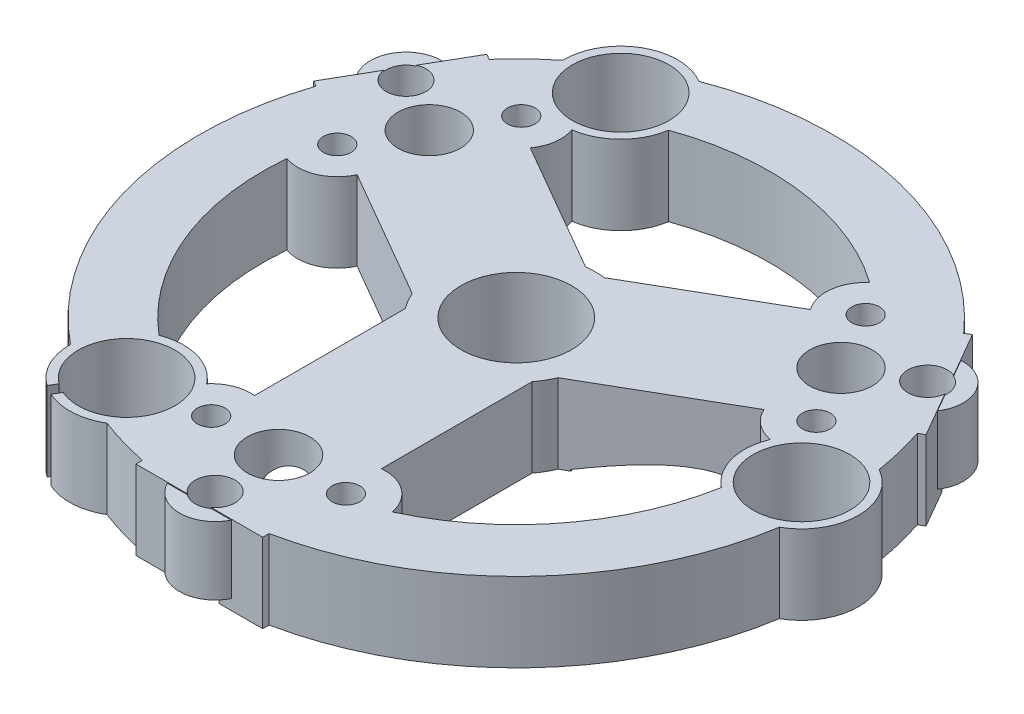
SolidWorks part; units mm, degrees
note: '?' marks a value the reader was unsure of.
other "Moving Tensegrity Frame"
ref_plane "Front Plane" through (0, 0, 0) normal (0, 0, 1) x (1, 0, 0)
ref_plane "Top Plane" through (0, 0, 0) normal (0, 1, 0) x (1, 0, 0)
ref_plane "Right Plane" through (0, 0, 0) normal (1, 0, 0) x (0, 0, -1)
sketch3d "Main Profile Sketch datum points"
  point P0 (0, 96, 0)
  point P1 (10, 96, 0)
  point P2 (0, 96, 10)
ref_plane "Main Profile Sketch plane" through (0, 96, 0) normal (0, -1, 0) x (-1, 0, 0)
sketch "Main Profile Sketch" plane through (0, 96, 0) normal (0, -1, 0) x (-1, 0, 0)
  line L0 (77.2684, -37.7328) -> (76.7153, -36.7748)
  line L1 (77.9277, -36.0748) -> (78.4808, -37.0328)
  line L2 (94.9327, 13.0718) -> (94.2328, 12.6677)
  line L3 (92.1817, 17.8367) -> (94.9327, 13.0718)
  line L4 (86.9327, 26.9282) -> (89.6837, 22.1633)
  line L5 (86.2328, 26.5241) -> (86.9327, 26.9282)
  line L6 (25.6506, 26.9282) -> (26.3505, 26.5241)
  line L7 (22.8996, 22.1633) -> (25.6506, 26.9282)
  line L8 (17.6506, 13.0718) -> (20.4016, 17.8367)
  line L9 (18.3505, 12.6677) -> (17.6506, 13.0718)
  line L10 (48.2917, -40) -> (48.2917, -39.1918)
  line L11 (53.7937, -40) -> (48.2917, -40)
  line L12 (64.2917, -40) -> (58.7897, -40)
  line L13 (64.2917, -39.1918) -> (64.2917, -40)
  line L14 (57.4878, 9.9282) -> (73.964, 19.4407)
  line L15 (38.6193, 19.4407) -> (55.0955, 9.9282)
  line L16 (64.2917, -6) -> (64.2917, -25.0251)
  line L17 (81.964, 5.5843) -> (65.4878, -3.9282)
  line L18 (47.0955, -3.9282) -> (30.6193, 5.5843)
  line L19 (48.2917, -25.0251) -> (48.2917, -6)
  arc A0 (77.9277, -36.0748) -> (76.7153, -36.7748) centre (74.2917, -31.1769) ccw
  arc A1 (78.4808, -37.0328) -> (81.4908, -31.0645) centre (74.2917, -31.1769) ccw
  arc A2 (81.4908, -31.0645) -> (94.2328, 12.6677) centre (56.2917, 0) ccw
  arc A3 (89.6837, 22.1633) -> (92.1817, 17.8367) centre (89.2006, 19) ccw
  arc A4 (86.2328, 26.5241) -> (81.4908, 31.0645) centre (56.2917, 0) ccw
  arc A5 (81.4908, 31.0645) -> (70.5948, 37.3553) centre (74.2917, 31.1769) ccw
  arc A6 (70.5948, 37.3553) -> (26.3505, 26.5241) centre (56.2917, 0) ccw
  arc A7 (20.4016, 17.8367) -> (22.8996, 22.1633) centre (23.3827, 19) ccw
  arc A8 (18.3505, 12.6677) -> (16.7894, 6.2908) centre (56.2917, 0) ccw
  arc A9 (16.7894, 6.2908) -> (16.7894, -6.2908) centre (20.2917, 0) ccw
  arc A10 (16.7894, -6.2908) -> (48.2917, -39.1918) centre (56.2917, 0) ccw
  arc A11 (58.7897, -40) -> (53.7937, -40) centre (56.2917, -38) ccw
  arc A12 (64.2917, -39.1918) -> (70.5948, -37.3553) centre (56.2917, 0) ccw
  arc A13 (70.5948, -37.3553) -> (77.2684, -37.7328) centre (74.2917, -31.1769) ccw
  circle A14 centre (74.2917, 31.1769) radius 6.1
  arc A15 (38.6193, 19.4407) -> (37.8344, 26.1406) centre (34.5609, 22.3612) ccw
  arc A16 (67.1737, 30.0929) -> (37.8344, 26.1406) centre (56.2917, 0) ccw
  arc A17 (67.1737, 30.0929) -> (73.314, 24.0436) centre (74.2917, 31.1769) ccw
  arc A18 (73.314, 24.0436) -> (73.964, 19.4407) centre (78.0224, 22.3612) ccw
  arc A19 (57.4878, 9.9282) -> (55.0955, 9.9282) centre (56.2917, 0) ccw
  arc A20 (68.6029, -26.7636) -> (64.2917, -25.0251) centre (64.7917, -30) ccw
  arc A21 (64.2917, -6) -> (65.4878, -3.9282) centre (56.2917, 0) ccw
  arc A22 (81.964, 5.5843) -> (88.1587, 2.9141) centre (86.5224, 7.6388) ccw
  arc A23 (76.9118, -24.4706) -> (88.1587, 2.9141) centre (56.2917, 0) ccw
  arc A24 (76.9118, -24.4706) -> (68.6029, -26.7636) centre (74.2917, -31.1769) ccw
  circle A25 centre (20.2917, 0) radius 6.1
  arc A26 (48.2917, -25.0251) -> (42.8818, -29.0547) centre (47.7917, -30) ccw
  arc A27 (24.7894, -5.6223) -> (42.8818, -29.0547) centre (56.2917, 0) ccw
  arc A28 (24.7894, -5.6223) -> (26.9581, 2.7199) centre (20.2917, 0) ccw
  arc A29 (26.9581, 2.7199) -> (30.6193, 5.5843) centre (26.0609, 7.6388) ccw
  arc A30 (47.0955, -3.9282) -> (48.2917, -6) centre (56.2917, 0) ccw
extrude "Main Extrusion" add sketch "Main Profile Sketch" against normal blind 1 separate body
sketch3d "Detail Profile 2 Sketch datum points"
  point P0 (0, 97, 0)
  point P1 (10, 97, 0)
  point P2 (0, 97, 10)
ref_plane "Detail Profile 2 Sketch plane" through (0, 97, 0) normal (0, -1, 0) x (-1, 0, 0)
sketch "Detail Profile 2 Sketch" plane through (0, 97, 0) normal (0, -1, 0) x (-1, 0, 0)
  line L0 (77.2684, -37.7328) -> (76.7153, -36.7748)
  line L1 (77.9277, -36.0748) -> (78.4808, -37.0328)
  line L2 (94.9327, 13.0718) -> (94.2328, 12.6677)
  line L3 (92.1817, 17.8367) -> (94.9327, 13.0718)
  line L4 (86.9327, 26.9282) -> (89.6837, 22.1633)
  line L5 (86.2328, 26.5241) -> (86.9327, 26.9282)
  line L6 (25.6506, 26.9282) -> (26.3505, 26.5241)
  line L7 (22.8996, 22.1633) -> (25.6506, 26.9282)
  line L8 (17.6506, 13.0718) -> (20.4016, 17.8367)
  line L9 (18.3505, 12.6677) -> (17.6506, 13.0718)
  line L10 (48.2917, -40) -> (48.2917, -39.1918)
  line L11 (53.7937, -40) -> (48.2917, -40)
  line L12 (64.2917, -40) -> (58.7897, -40)
  line L13 (64.2917, -39.1918) -> (64.2917, -40)
  line L14 (79.1224, 17.3833) -> (79.1224, 12.6167)
  line L15 (57.4878, 9.9282) -> (73.964, 19.4407)
  line L16 (38.6193, 19.4407) -> (55.0955, 9.9282)
  line L17 (64.2917, -6) -> (64.2917, -25.0251)
  line L18 (81.964, 5.5843) -> (65.4878, -3.9282)
  line L19 (59.9306, -28.4637) -> (55.8027, -26.0804)
  line L20 (29.8219, 11.0804) -> (33.9499, 13.4637)
  line L21 (47.0955, -3.9282) -> (30.6193, 5.5843)
  line L22 (48.2917, -25.0251) -> (48.2917, -6)
  arc A0 (77.9277, -36.0748) -> (76.7153, -36.7748) centre (74.2917, -31.1769) ccw
  arc A1 (78.4808, -37.0328) -> (81.4908, -31.0645) centre (74.2917, -31.1769) ccw
  arc A2 (81.4908, -31.0645) -> (94.2328, 12.6677) centre (56.2917, 0) ccw
  arc A3 (89.6837, 22.1633) -> (92.1817, 17.8367) centre (89.2006, 19) ccw
  arc A4 (86.2328, 26.5241) -> (81.4908, 31.0645) centre (56.2917, 0) ccw
  arc A5 (81.4908, 31.0645) -> (70.5948, 37.3553) centre (74.2917, 31.1769) ccw
  arc A6 (70.5948, 37.3553) -> (26.3505, 26.5241) centre (56.2917, 0) ccw
  arc A7 (20.4016, 17.8367) -> (22.8996, 22.1633) centre (23.3827, 19) ccw
  arc A8 (18.3505, 12.6677) -> (16.7894, 6.2908) centre (56.2917, 0) ccw
  arc A9 (16.7894, 6.2908) -> (16.7894, -6.2908) centre (20.2917, 0) ccw
  arc A10 (16.7894, -6.2908) -> (48.2917, -39.1918) centre (56.2917, 0) ccw
  arc A11 (58.7897, -40) -> (53.7937, -40) centre (56.2917, -38) ccw
  arc A12 (64.2917, -39.1918) -> (70.5948, -37.3553) centre (56.2917, 0) ccw
  arc A13 (70.5948, -37.3553) -> (77.2684, -37.7328) centre (74.2917, -31.1769) ccw
  arc A14 (79.1224, 12.6167) -> (79.1224, 17.3833) centre (82.2724, 15) ccw
  circle A15 centre (74.2917, 31.1769) radius 6.1
  arc A16 (38.6193, 19.4407) -> (37.8344, 26.1406) centre (34.5609, 22.3612) ccw
  arc A17 (67.1737, 30.0929) -> (37.8344, 26.1406) centre (56.2917, 0) ccw
  arc A18 (67.1737, 30.0929) -> (73.314, 24.0436) centre (74.2917, 31.1769) ccw
  arc A19 (73.314, 24.0436) -> (73.964, 19.4407) centre (78.0224, 22.3612) ccw
  arc A20 (57.4878, 9.9282) -> (55.0955, 9.9282) centre (56.2917, 0) ccw
  arc A21 (68.6029, -26.7636) -> (64.2917, -25.0251) centre (64.7917, -30) ccw
  arc A22 (64.2917, -6) -> (65.4878, -3.9282) centre (56.2917, 0) ccw
  arc A23 (81.964, 5.5843) -> (88.1587, 2.9141) centre (86.5224, 7.6388) ccw
  arc A24 (76.9118, -24.4706) -> (88.1587, 2.9141) centre (56.2917, 0) ccw
  arc A25 (76.9118, -24.4706) -> (68.6029, -26.7636) centre (74.2917, -31.1769) ccw
  arc A26 (55.8027, -26.0804) -> (52.3417, -30) centre (56.2917, -30) ccw
  arc A27 (52.3417, -30) -> (59.9306, -28.4637) centre (56.2917, -30) ccw
  arc A28 (33.9499, 13.4637) -> (26.3609, 15) centre (30.3109, 15) ccw
  arc A29 (26.3609, 15) -> (29.8219, 11.0804) centre (30.3109, 15) ccw
  circle A30 centre (20.2917, 0) radius 6.1
  arc A31 (48.2917, -25.0251) -> (42.8818, -29.0547) centre (47.7917, -30) ccw
  arc A32 (24.7894, -5.6223) -> (42.8818, -29.0547) centre (56.2917, 0) ccw
  arc A33 (24.7894, -5.6223) -> (26.9581, 2.7199) centre (20.2917, 0) ccw
  arc A34 (26.9581, 2.7199) -> (30.6193, 5.5843) centre (26.0609, 7.6388) ccw
  arc A35 (47.0955, -3.9282) -> (48.2917, -6) centre (56.2917, 0) ccw
extrude "Detail Extrusion 2" add sketch "Detail Profile 2 Sketch" against normal blind 0.31
sketch3d "Detail Profile 3 Sketch datum points"
  point P0 (0, 97.31, 0)
  point P1 (10, 97.31, 0)
  point P2 (0, 97.31, 10)
ref_plane "Detail Profile 3 Sketch plane" through (0, 97.31, 0) normal (0, -1, 0) x (-1, 0, 0)
sketch "Detail Profile 3 Sketch" plane through (0, 97.31, 0) normal (0, -1, 0) x (-1, 0, 0)
  line L0 (77.2684, -37.7328) -> (76.7153, -36.7748)
  line L1 (77.9277, -36.0748) -> (78.4808, -37.0328)
  line L2 (94.9327, 13.0718) -> (94.2328, 12.6677)
  line L3 (92.9482, 16.5089) -> (94.9327, 13.0718)
  line L4 (86.9327, 26.9282) -> (88.9171, 23.4911)
  line L5 (86.2328, 26.5241) -> (86.9327, 26.9282)
  line L6 (25.6506, 26.9282) -> (26.3505, 26.5241)
  line L7 (23.6662, 23.4911) -> (25.6506, 26.9282)
  line L8 (17.6506, 13.0718) -> (19.6351, 16.5089)
  line L9 (18.3505, 12.6677) -> (17.6506, 13.0718)
  line L10 (48.2917, -40) -> (48.2917, -39.1918)
  line L11 (52.2605, -40) -> (48.2917, -40)
  line L12 (64.2917, -40) -> (60.3228, -40)
  line L13 (64.2917, -39.1918) -> (64.2917, -40)
  line L14 (79.1224, 17.3833) -> (79.1224, 12.6167)
  line L15 (57.4878, 9.9282) -> (73.964, 19.4407)
  line L16 (38.6193, 19.4407) -> (55.0955, 9.9282)
  line L17 (64.2917, -6) -> (64.2917, -25.0251)
  line L18 (81.964, 5.5843) -> (65.4878, -3.9282)
  line L19 (59.9306, -28.4637) -> (55.8027, -26.0804)
  line L20 (29.8219, 11.0804) -> (33.9499, 13.4637)
  line L21 (47.0955, -3.9282) -> (30.6193, 5.5843)
  line L22 (48.2917, -25.0251) -> (48.2917, -6)
  arc A0 (77.9277, -36.0748) -> (76.7153, -36.7748) centre (74.2917, -31.1769) ccw
  arc A1 (78.4808, -37.0328) -> (81.4908, -31.0645) centre (74.2917, -31.1769) ccw
  arc A2 (81.4908, -31.0645) -> (94.2328, 12.6677) centre (56.2917, 0) ccw
  arc A3 (92.9482, 16.5089) -> (88.9171, 23.4911) centre (89.2006, 19) ccw
  arc A4 (86.2328, 26.5241) -> (81.4908, 31.0645) centre (56.2917, 0) ccw
  arc A5 (81.4908, 31.0645) -> (70.5948, 37.3553) centre (74.2917, 31.1769) ccw
  arc A6 (70.5948, 37.3553) -> (26.3505, 26.5241) centre (56.2917, 0) ccw
  arc A7 (23.6662, 23.4911) -> (19.6351, 16.5089) centre (23.3827, 19) ccw
  arc A8 (18.3505, 12.6677) -> (16.7894, 6.2908) centre (56.2917, 0) ccw
  arc A9 (16.7894, 6.2908) -> (16.7894, -6.2908) centre (20.2917, 0) ccw
  arc A10 (16.7894, -6.2908) -> (48.2917, -39.1918) centre (56.2917, 0) ccw
  arc A11 (52.2605, -40) -> (60.3228, -40) centre (56.2917, -38) ccw
  arc A12 (64.2917, -39.1918) -> (70.5948, -37.3553) centre (56.2917, 0) ccw
  arc A13 (70.5948, -37.3553) -> (77.2684, -37.7328) centre (74.2917, -31.1769) ccw
  circle A14 centre (89.2006, 19) radius 2.5
  arc A15 (79.1224, 12.6167) -> (79.1224, 17.3833) centre (82.2724, 15) ccw
  circle A16 centre (74.2917, 31.1769) radius 6.1
  arc A17 (38.6193, 19.4407) -> (37.8344, 26.1406) centre (34.5609, 22.3612) ccw
  arc A18 (67.1737, 30.0929) -> (37.8344, 26.1406) centre (56.2917, 0) ccw
  arc A19 (67.1737, 30.0929) -> (73.314, 24.0436) centre (74.2917, 31.1769) ccw
  arc A20 (73.314, 24.0436) -> (73.964, 19.4407) centre (78.0224, 22.3612) ccw
  arc A21 (57.4878, 9.9282) -> (55.0955, 9.9282) centre (56.2917, 0) ccw
  arc A22 (68.6029, -26.7636) -> (64.2917, -25.0251) centre (64.7917, -30) ccw
  arc A23 (64.2917, -6) -> (65.4878, -3.9282) centre (56.2917, 0) ccw
  arc A24 (81.964, 5.5843) -> (88.1587, 2.9141) centre (86.5224, 7.6388) ccw
  arc A25 (76.9118, -24.4706) -> (88.1587, 2.9141) centre (56.2917, 0) ccw
  arc A26 (76.9118, -24.4706) -> (68.6029, -26.7636) centre (74.2917, -31.1769) ccw
  arc A27 (55.8027, -26.0804) -> (52.3417, -30) centre (56.2917, -30) ccw
  arc A28 (52.3417, -30) -> (59.9306, -28.4637) centre (56.2917, -30) ccw
  circle A29 centre (56.2917, -38) radius 2.5
  arc A30 (33.9499, 13.4637) -> (26.3609, 15) centre (30.3109, 15) ccw
  arc A31 (26.3609, 15) -> (29.8219, 11.0804) centre (30.3109, 15) ccw
  circle A32 centre (23.3827, 19) radius 2.5
  circle A33 centre (20.2917, 0) radius 6.1
  arc A34 (48.2917, -25.0251) -> (42.8818, -29.0547) centre (47.7917, -30) ccw
  arc A35 (24.7894, -5.6223) -> (42.8818, -29.0547) centre (56.2917, 0) ccw
  arc A36 (24.7894, -5.6223) -> (26.9581, 2.7199) centre (20.2917, 0) ccw
  arc A37 (26.9581, 2.7199) -> (30.6193, 5.5843) centre (26.0609, 7.6388) ccw
  arc A38 (47.0955, -3.9282) -> (48.2917, -6) centre (56.2917, 0) ccw
extrude "Detail Extrusion 3" add sketch "Detail Profile 3 Sketch" against normal blind 0.4
sketch3d "Detail Profile 4 Sketch datum points"
  point P0 (0, 97.71, 0)
  point P1 (10, 97.71, 0)
  point P2 (0, 97.71, 10)
ref_plane "Detail Profile 4 Sketch plane" through (0, 97.71, 0) normal (0, -1, 0) x (-1, 0, 0)
sketch "Detail Profile 4 Sketch" plane through (0, 97.71, 0) normal (0, -1, 0) x (-1, 0, 0)
  line L0 (77.2684, -37.7328) -> (76.7153, -36.7748)
  line L1 (77.9277, -36.0748) -> (78.4808, -37.0328)
  line L2 (94.9327, 13.0718) -> (94.2328, 12.6677)
  line L3 (92.9482, 16.5089) -> (94.9327, 13.0718)
  line L4 (86.9327, 26.9282) -> (88.9171, 23.4911)
  line L5 (86.2328, 26.5241) -> (86.9327, 26.9282)
  line L6 (25.6506, 26.9282) -> (26.3505, 26.5241)
  line L7 (23.6662, 23.4911) -> (25.6506, 26.9282)
  line L8 (17.6506, 13.0718) -> (19.6351, 16.5089)
  line L9 (18.3505, 12.6677) -> (17.6506, 13.0718)
  line L10 (48.2917, -40) -> (48.2917, -39.1918)
  line L11 (52.2605, -40) -> (48.2917, -40)
  line L12 (64.2917, -40) -> (60.3228, -40)
  line L13 (64.2917, -39.1918) -> (64.2917, -40)
  line L14 (57.4878, 9.9282) -> (73.964, 19.4407)
  line L15 (38.6193, 19.4407) -> (55.0955, 9.9282)
  line L16 (64.2917, -6) -> (64.2917, -25.0251)
  line L17 (81.964, 5.5843) -> (65.4878, -3.9282)
  line L18 (47.0955, -3.9282) -> (30.6193, 5.5843)
  line L19 (48.2917, -25.0251) -> (48.2917, -6)
  arc A0 (77.9277, -36.0748) -> (76.7153, -36.7748) centre (74.2917, -31.1769) ccw
  arc A1 (78.4808, -37.0328) -> (81.4908, -31.0645) centre (74.2917, -31.1769) ccw
  arc A2 (81.4908, -31.0645) -> (94.2328, 12.6677) centre (56.2917, 0) ccw
  arc A3 (92.9482, 16.5089) -> (88.9171, 23.4911) centre (89.2006, 19) ccw
  arc A4 (86.2328, 26.5241) -> (81.4908, 31.0645) centre (56.2917, 0) ccw
  arc A5 (81.4908, 31.0645) -> (70.5948, 37.3553) centre (74.2917, 31.1769) ccw
  arc A6 (70.5948, 37.3553) -> (26.3505, 26.5241) centre (56.2917, 0) ccw
  arc A7 (23.6662, 23.4911) -> (19.6351, 16.5089) centre (23.3827, 19) ccw
  arc A8 (18.3505, 12.6677) -> (16.7894, 6.2908) centre (56.2917, 0) ccw
  arc A9 (16.7894, 6.2908) -> (16.7894, -6.2908) centre (20.2917, 0) ccw
  arc A10 (16.7894, -6.2908) -> (48.2917, -39.1918) centre (56.2917, 0) ccw
  arc A11 (52.2605, -40) -> (60.3228, -40) centre (56.2917, -38) ccw
  arc A12 (64.2917, -39.1918) -> (70.5948, -37.3553) centre (56.2917, 0) ccw
  arc A13 (70.5948, -37.3553) -> (77.2684, -37.7328) centre (74.2917, -31.1769) ccw
  circle A14 centre (89.2006, 19) radius 2.5
  circle A15 centre (82.2724, 15) radius 3.95
  circle A16 centre (74.2917, 31.1769) radius 6.1
  arc A17 (38.6193, 19.4407) -> (37.8344, 26.1406) centre (34.5609, 22.3612) ccw
  arc A18 (67.1737, 30.0929) -> (37.8344, 26.1406) centre (56.2917, 0) ccw
  arc A19 (67.1737, 30.0929) -> (73.314, 24.0436) centre (74.2917, 31.1769) ccw
  arc A20 (73.314, 24.0436) -> (73.964, 19.4407) centre (78.0224, 22.3612) ccw
  arc A21 (57.4878, 9.9282) -> (55.0955, 9.9282) centre (56.2917, 0) ccw
  arc A22 (68.6029, -26.7636) -> (64.2917, -25.0251) centre (64.7917, -30) ccw
  arc A23 (64.2917, -6) -> (65.4878, -3.9282) centre (56.2917, 0) ccw
  arc A24 (81.964, 5.5843) -> (88.1587, 2.9141) centre (86.5224, 7.6388) ccw
  arc A25 (76.9118, -24.4706) -> (88.1587, 2.9141) centre (56.2917, 0) ccw
  arc A26 (76.9118, -24.4706) -> (68.6029, -26.7636) centre (74.2917, -31.1769) ccw
  circle A27 centre (56.2917, -30) radius 3.95
  circle A28 centre (56.2917, -38) radius 2.5
  circle A29 centre (30.3109, 15) radius 3.95
  circle A30 centre (23.3827, 19) radius 2.5
  circle A31 centre (20.2917, 0) radius 6.1
  arc A32 (48.2917, -25.0251) -> (42.8818, -29.0547) centre (47.7917, -30) ccw
  arc A33 (24.7894, -5.6223) -> (42.8818, -29.0547) centre (56.2917, 0) ccw
  arc A34 (24.7894, -5.6223) -> (26.9581, 2.7199) centre (20.2917, 0) ccw
  arc A35 (26.9581, 2.7199) -> (30.6193, 5.5843) centre (26.0609, 7.6388) ccw
  arc A36 (47.0955, -3.9282) -> (48.2917, -6) centre (56.2917, 0) ccw
extrude "Detail Extrusion 4" add sketch "Detail Profile 4 Sketch" against normal blind 2.99
sketch3d "Detail Profile 5 Sketch datum points"
  point P0 (0, 100.7, 0)
  point P1 (10, 100.7, 0)
  point P2 (0, 100.7, 10)
ref_plane "Detail Profile 5 Sketch plane" through (0, 100.7, 0) normal (0, -1, 0) x (-1, 0, 0)
sketch "Detail Profile 5 Sketch" plane through (0, 100.7, 0) normal (0, -1, 0) x (-1, 0, 0)
  line L0 (77.2684, -37.7328) -> (76.7153, -36.7748)
  line L1 (77.9277, -36.0748) -> (78.4808, -37.0328)
  line L2 (94.9327, 13.0718) -> (94.2328, 12.6677)
  line L3 (92.9482, 16.5089) -> (94.9327, 13.0718)
  line L4 (86.9327, 26.9282) -> (88.9171, 23.4911)
  line L5 (86.2328, 26.5241) -> (86.9327, 26.9282)
  line L6 (25.6506, 26.9282) -> (26.3505, 26.5241)
  line L7 (23.6662, 23.4911) -> (25.6506, 26.9282)
  line L8 (17.6506, 13.0718) -> (19.6351, 16.5089)
  line L9 (18.3505, 12.6677) -> (17.6506, 13.0718)
  line L10 (48.2917, -40) -> (48.2917, -39.1918)
  line L11 (52.2605, -40) -> (48.2917, -40)
  line L12 (64.2917, -40) -> (60.3228, -40)
  line L13 (64.2917, -39.1918) -> (64.2917, -40)
  line L14 (57.4878, 9.9282) -> (73.964, 19.4407)
  line L15 (38.6193, 19.4407) -> (55.0955, 9.9282)
  line L16 (64.2917, -6) -> (64.2917, -25.0251)
  line L17 (81.964, 5.5843) -> (65.4878, -3.9282)
  line L18 (47.0955, -3.9282) -> (30.6193, 5.5843)
  line L19 (48.2917, -25.0251) -> (48.2917, -6)
  arc A0 (77.9277, -36.0748) -> (76.7153, -36.7748) centre (74.2917, -31.1769) ccw
  arc A1 (78.4808, -37.0328) -> (81.4908, -31.0645) centre (74.2917, -31.1769) ccw
  arc A2 (81.4908, -31.0645) -> (94.2328, 12.6677) centre (56.2917, 0) ccw
  arc A3 (92.9482, 16.5089) -> (88.9171, 23.4911) centre (89.2006, 19) ccw
  arc A4 (86.2328, 26.5241) -> (81.4908, 31.0645) centre (56.2917, 0) ccw
  arc A5 (81.4908, 31.0645) -> (70.5948, 37.3553) centre (74.2917, 31.1769) ccw
  arc A6 (70.5948, 37.3553) -> (26.3505, 26.5241) centre (56.2917, 0) ccw
  arc A7 (23.6662, 23.4911) -> (19.6351, 16.5089) centre (23.3827, 19) ccw
  arc A8 (18.3505, 12.6677) -> (16.7894, 6.2908) centre (56.2917, 0) ccw
  arc A9 (16.7894, 6.2908) -> (16.7894, -6.2908) centre (20.2917, 0) ccw
  arc A10 (16.7894, -6.2908) -> (48.2917, -39.1918) centre (56.2917, 0) ccw
  arc A11 (52.2605, -40) -> (60.3228, -40) centre (56.2917, -38) ccw
  arc A12 (64.2917, -39.1918) -> (70.5948, -37.3553) centre (56.2917, 0) ccw
  arc A13 (70.5948, -37.3553) -> (77.2684, -37.7328) centre (74.2917, -31.1769) ccw
  circle A14 centre (78.0224, 22.3612) radius 1.1
  circle A15 centre (89.2006, 19) radius 2.5
  circle A16 centre (86.5224, 7.6388) radius 1.1
  circle A17 centre (82.2724, 15) radius 3.95
  circle A18 centre (74.2917, 31.1769) radius 6.1
  arc A19 (38.6193, 19.4407) -> (37.8344, 26.1406) centre (34.5609, 22.3612) ccw
  arc A20 (67.1737, 30.0929) -> (37.8344, 26.1406) centre (56.2917, 0) ccw
  arc A21 (67.1737, 30.0929) -> (73.314, 24.0436) centre (74.2917, 31.1769) ccw
  arc A22 (73.314, 24.0436) -> (73.964, 19.4407) centre (78.0224, 22.3612) ccw
  arc A23 (57.4878, 9.9282) -> (55.0955, 9.9282) centre (56.2917, 0) ccw
  arc A24 (68.6029, -26.7636) -> (64.2917, -25.0251) centre (64.7917, -30) ccw
  arc A25 (64.2917, -6) -> (65.4878, -3.9282) centre (56.2917, 0) ccw
  arc A26 (81.964, 5.5843) -> (88.1587, 2.9141) centre (86.5224, 7.6388) ccw
  arc A27 (76.9118, -24.4706) -> (88.1587, 2.9141) centre (56.2917, 0) ccw
  arc A28 (76.9118, -24.4706) -> (68.6029, -26.7636) centre (74.2917, -31.1769) ccw
  circle A29 centre (64.7917, -30) radius 1.1
  circle A30 centre (56.2917, -30) radius 3.95
  circle A31 centre (56.2917, -38) radius 2.5
  circle A32 centre (34.5609, 22.3612) radius 1.1
  circle A33 centre (30.3109, 15) radius 3.95
  circle A34 centre (26.0609, 7.6388) radius 1.1
  circle A35 centre (23.3827, 19) radius 2.5
  circle A36 centre (20.2917, 0) radius 6.1
  arc A37 (48.2917, -25.0251) -> (42.8818, -29.0547) centre (47.7917, -30) ccw
  arc A38 (24.7894, -5.6223) -> (42.8818, -29.0547) centre (56.2917, 0) ccw
  arc A39 (24.7894, -5.6223) -> (26.9581, 2.7199) centre (20.2917, 0) ccw
  arc A40 (26.9581, 2.7199) -> (30.6193, 5.5843) centre (26.0609, 7.6388) ccw
  arc A41 (47.0955, -3.9282) -> (48.2917, -6) centre (56.2917, 0) ccw
  circle A42 centre (47.7917, -30) radius 1.1
extrude "Detail Extrusion 5" add sketch "Detail Profile 5 Sketch" against normal blind 1.3
sketch3d "Detail Profile 6 Sketch datum points"
  point P0 (0, 102, 0)
  point P1 (10, 102, 0)
  point P2 (0, 102, 10)
ref_plane "Detail Profile 6 Sketch plane" through (0, 102, 0) normal (0, -1, 0) x (-1, 0, 0)
sketch "Detail Profile 6 Sketch" plane through (0, 102, 0) normal (0, -1, 0) x (-1, 0, 0)
  line L0 (77.2684, -37.7328) -> (76.7153, -36.7748)
  line L1 (77.9277, -36.0748) -> (78.4808, -37.0328)
  line L2 (94.9327, 13.0718) -> (94.2328, 12.6677)
  line L3 (92.9482, 16.5089) -> (94.9327, 13.0718)
  line L4 (86.9327, 26.9282) -> (88.9171, 23.4911)
  line L5 (86.2328, 26.5241) -> (86.9327, 26.9282)
  line L6 (25.6506, 26.9282) -> (26.3505, 26.5241)
  line L7 (23.6662, 23.4911) -> (25.6506, 26.9282)
  line L8 (17.6506, 13.0718) -> (19.6351, 16.5089)
  line L9 (18.3505, 12.6677) -> (17.6506, 13.0718)
  line L10 (48.2917, -40) -> (48.2917, -39.1918)
  line L11 (52.2605, -40) -> (48.2917, -40)
  line L12 (64.2917, -40) -> (60.3228, -40)
  line L13 (64.2917, -39.1918) -> (64.2917, -40)
  line L14 (57.4878, 9.9282) -> (73.964, 19.4407)
  line L15 (38.6193, 19.4407) -> (55.0955, 9.9282)
  line L16 (64.2917, -6) -> (64.2917, -25.0251)
  line L17 (81.964, 5.5843) -> (65.4878, -3.9282)
  line L18 (47.0955, -3.9282) -> (30.6193, 5.5843)
  line L19 (48.2917, -25.0251) -> (48.2917, -6)
  arc A0 (77.9277, -36.0748) -> (76.7153, -36.7748) centre (74.2917, -31.1769) ccw
  arc A1 (78.4808, -37.0328) -> (81.4908, -31.0645) centre (74.2917, -31.1769) ccw
  arc A2 (81.4908, -31.0645) -> (94.2328, 12.6677) centre (56.2917, 0) ccw
  arc A3 (92.9482, 16.5089) -> (88.9171, 23.4911) centre (89.2006, 19) ccw
  arc A4 (86.2328, 26.5241) -> (81.4908, 31.0645) centre (56.2917, 0) ccw
  arc A5 (81.4908, 31.0645) -> (70.5948, 37.3553) centre (74.2917, 31.1769) ccw
  arc A6 (70.5948, 37.3553) -> (26.3505, 26.5241) centre (56.2917, 0) ccw
  arc A7 (23.6662, 23.4911) -> (19.6351, 16.5089) centre (23.3827, 19) ccw
  arc A8 (18.3505, 12.6677) -> (16.7894, 6.2908) centre (56.2917, 0) ccw
  arc A9 (16.7894, 6.2908) -> (16.7894, -6.2908) centre (20.2917, 0) ccw
  arc A10 (16.7894, -6.2908) -> (48.2917, -39.1918) centre (56.2917, 0) ccw
  arc A11 (52.2605, -40) -> (60.3228, -40) centre (56.2917, -38) ccw
  arc A12 (64.2917, -39.1918) -> (70.5948, -37.3553) centre (56.2917, 0) ccw
  arc A13 (70.5948, -37.3553) -> (77.2684, -37.7328) centre (74.2917, -31.1769) ccw
  circle A14 centre (78.0224, 22.3612) radius 1.75
  circle A15 centre (89.2006, 19) radius 2.5
  circle A16 centre (86.5224, 7.6388) radius 1.75
  circle A17 centre (82.2724, 15) radius 3.95
  circle A18 centre (74.2917, 31.1769) radius 6.1
  arc A19 (38.6193, 19.4407) -> (37.8344, 26.1406) centre (34.5609, 22.3612) ccw
  arc A20 (67.1737, 30.0929) -> (37.8344, 26.1406) centre (56.2917, 0) ccw
  arc A21 (67.1737, 30.0929) -> (73.314, 24.0436) centre (74.2917, 31.1769) ccw
  arc A22 (73.314, 24.0436) -> (73.964, 19.4407) centre (78.0224, 22.3612) ccw
  arc A23 (57.4878, 9.9282) -> (55.0955, 9.9282) centre (56.2917, 0) ccw
  arc A24 (68.6029, -26.7636) -> (64.2917, -25.0251) centre (64.7917, -30) ccw
  arc A25 (64.2917, -6) -> (65.4878, -3.9282) centre (56.2917, 0) ccw
  arc A26 (81.964, 5.5843) -> (88.1587, 2.9141) centre (86.5224, 7.6388) ccw
  arc A27 (76.9118, -24.4706) -> (88.1587, 2.9141) centre (56.2917, 0) ccw
  arc A28 (76.9118, -24.4706) -> (68.6029, -26.7636) centre (74.2917, -31.1769) ccw
  circle A29 centre (64.7917, -30) radius 1.75
  circle A30 centre (56.2917, -30) radius 3.95
  circle A31 centre (56.2917, -38) radius 2.5
  circle A32 centre (34.5609, 22.3612) radius 1.75
  circle A33 centre (30.3109, 15) radius 3.95
  circle A34 centre (26.0609, 7.6388) radius 1.75
  circle A35 centre (23.3827, 19) radius 2.5
  circle A36 centre (20.2917, 0) radius 6.1
  arc A37 (48.2917, -25.0251) -> (42.8818, -29.0547) centre (47.7917, -30) ccw
  arc A38 (24.7894, -5.6223) -> (42.8818, -29.0547) centre (56.2917, 0) ccw
  arc A39 (24.7894, -5.6223) -> (26.9581, 2.7199) centre (20.2917, 0) ccw
  arc A40 (26.9581, 2.7199) -> (30.6193, 5.5843) centre (26.0609, 7.6388) ccw
  arc A41 (47.0955, -3.9282) -> (48.2917, -6) centre (56.2917, 0) ccw
  circle A42 centre (47.7917, -30) radius 1.75
extrude "Detail Extrusion 6" add sketch "Detail Profile 6 Sketch" against normal blind 3.89
sketch3d "Detail Profile 7 Sketch datum points"
  point P0 (0, 105.89, 0)
  point P1 (10, 105.89, 0)
  point P2 (0, 105.89, 10)
ref_plane "Detail Profile 7 Sketch plane" through (0, 105.89, 0) normal (0, -1, 0) x (-1, 0, 0)
sketch "Detail Profile 7 Sketch" plane through (0, 105.89, 0) normal (0, -1, 0) x (-1, 0, 0)
  line L0 (77.2684, -37.7328) -> (76.7153, -36.7748)
  line L1 (77.9277, -36.0748) -> (78.4808, -37.0328)
  line L2 (94.9327, 13.0718) -> (94.2328, 12.6677)
  line L3 (91.6827, 18.701) -> (94.9327, 13.0718)
  line L4 (86.9327, 26.9282) -> (90.1827, 21.299)
  line L5 (86.2328, 26.5241) -> (86.9327, 26.9282)
  line L6 (25.6506, 26.9282) -> (26.3505, 26.5241)
  line L7 (22.4006, 21.299) -> (25.6506, 26.9282)
  line L8 (17.6506, 13.0718) -> (20.9006, 18.701)
  line L9 (18.3505, 12.6677) -> (17.6506, 13.0718)
  line L10 (48.2917, -40) -> (48.2917, -39.1918)
  line L11 (54.7917, -40) -> (48.2917, -40)
  line L12 (64.2917, -40) -> (57.7917, -40)
  line L13 (64.2917, -39.1918) -> (64.2917, -40)
  line L14 (57.4878, 9.9282) -> (73.964, 19.4407)
  line L15 (38.6193, 19.4407) -> (55.0955, 9.9282)
  line L16 (64.2917, -6) -> (64.2917, -25.0251)
  line L17 (81.964, 5.5843) -> (65.4878, -3.9282)
  line L18 (47.0955, -3.9282) -> (30.6193, 5.5843)
  line L19 (48.2917, -25.0251) -> (48.2917, -6)
  arc A0 (77.9277, -36.0748) -> (76.7153, -36.7748) centre (74.2917, -31.1769) ccw
  arc A1 (78.4808, -37.0328) -> (81.4908, -31.0645) centre (74.2917, -31.1769) ccw
  arc A2 (81.4908, -31.0645) -> (94.2328, 12.6677) centre (56.2917, 0) ccw
  arc A3 (89.2006, 21.5) -> (91.6827, 18.701) centre (89.2006, 19) ccw
  arc A4 (90.1827, 21.299) -> (89.2006, 21.5) centre (89.2006, 19) ccw
  arc A5 (86.2328, 26.5241) -> (81.4908, 31.0645) centre (56.2917, 0) ccw
  arc A6 (81.4908, 31.0645) -> (70.5948, 37.3553) centre (74.2917, 31.1769) ccw
  arc A7 (70.5948, 37.3553) -> (26.3505, 26.5241) centre (56.2917, 0) ccw
  arc A8 (23.3827, 21.5) -> (22.4006, 21.299) centre (23.3827, 19) ccw
  arc A9 (20.9006, 18.701) -> (23.3827, 21.5) centre (23.3827, 19) ccw
  arc A10 (18.3505, 12.6677) -> (16.7894, 6.2908) centre (56.2917, 0) ccw
  arc A11 (16.7894, 6.2908) -> (16.7894, -6.2908) centre (20.2917, 0) ccw
  arc A12 (16.7894, -6.2908) -> (48.2917, -39.1918) centre (56.2917, 0) ccw
  arc A13 (56.2917, -35.5) -> (54.7917, -40) centre (56.2917, -38) ccw
  arc A14 (57.7917, -40) -> (56.2917, -35.5) centre (56.2917, -38) ccw
  arc A15 (64.2917, -39.1918) -> (70.5948, -37.3553) centre (56.2917, 0) ccw
  arc A16 (70.5948, -37.3553) -> (77.2684, -37.7328) centre (74.2917, -31.1769) ccw
  circle A17 centre (78.0224, 22.3612) radius 1.75
  circle A18 centre (86.5224, 7.6388) radius 1.75
  circle A19 centre (82.2724, 15) radius 3.95
  circle A20 centre (74.2917, 31.1769) radius 6.1
  arc A21 (38.6193, 19.4407) -> (37.8344, 26.1406) centre (34.5609, 22.3612) ccw
  arc A22 (67.1737, 30.0929) -> (37.8344, 26.1406) centre (56.2917, 0) ccw
  arc A23 (67.1737, 30.0929) -> (73.314, 24.0436) centre (74.2917, 31.1769) ccw
  arc A24 (73.314, 24.0436) -> (73.964, 19.4407) centre (78.0224, 22.3612) ccw
  arc A25 (57.4878, 9.9282) -> (55.0955, 9.9282) centre (56.2917, 0) ccw
  arc A26 (68.6029, -26.7636) -> (64.2917, -25.0251) centre (64.7917, -30) ccw
  arc A27 (64.2917, -6) -> (65.4878, -3.9282) centre (56.2917, 0) ccw
  arc A28 (81.964, 5.5843) -> (88.1587, 2.9141) centre (86.5224, 7.6388) ccw
  arc A29 (76.9118, -24.4706) -> (88.1587, 2.9141) centre (56.2917, 0) ccw
  arc A30 (76.9118, -24.4706) -> (68.6029, -26.7636) centre (74.2917, -31.1769) ccw
  circle A31 centre (64.7917, -30) radius 1.75
  circle A32 centre (56.2917, -30) radius 3.95
  circle A33 centre (34.5609, 22.3612) radius 1.75
  circle A34 centre (30.3109, 15) radius 3.95
  circle A35 centre (26.0609, 7.6388) radius 1.75
  arc A36 (48.2917, -25.0251) -> (42.8818, -29.0547) centre (47.7917, -30) ccw
  arc A37 (24.7894, -5.6223) -> (42.8818, -29.0547) centre (56.2917, 0) ccw
  arc A38 (24.7894, -5.6223) -> (26.9581, 2.7199) centre (20.2917, 0) ccw
  arc A39 (26.9581, 2.7199) -> (30.6193, 5.5843) centre (26.0609, 7.6388) ccw
  arc A40 (47.0955, -3.9282) -> (48.2917, -6) centre (56.2917, 0) ccw
  circle A41 centre (47.7917, -30) radius 1.75
  circle A42 centre (20.2917, 0) radius 6.1
extrude "Detail Extrusion 7" add sketch "Detail Profile 7 Sketch" against normal blind 0.11
sketch3d "Compression Articulation Throat 61 axis line"
  line L0 (-90.6158, 106.3831, -16.1872) -> (-73.929, 95.6169, -13.8128) construction
ref_axis "Compression Articulation Throat 61 axis" through (-90.6158, 106.3831, -16.1872) along (0.8343, -0.5383, 0.1187)?
sketch3d "Compression Articulation Throat 61 Sketch datum points"
  point P0 (-82.2724, 101, -15)
  point P1 (-82.2724, 98.8462, -24.7653)
  point P2 (-73.929, 95.6169, -13.8128)
ref_plane "Compression Articulation Throat 61 Sketch plane" through (21.8481, 32.2924, -7.1221) normal (-0.5512, -0.8148, 0.1797) x (-0.8343, 0.5383, -0.1187)
sketch "Compression Articulation Throat 61 Sketch" plane through (21.8481, 32.2924, -7.1221) normal (-0.5512, -0.8148, 0.1797) x (-0.8343, 0.5383, -0.1187)
  line L0 (124.7935, -7.105) -> (124.7935, -4.805)
  line L1 (124.7935, -4.805) -> (101.7935, 1.915)
  line L2 (101.7935, 1.915) -> (101.7935, -7.105)
  line L3 (101.7935, -7.105) -> (124.7935, -7.105)
revolve "Compression Articulation Throat 61" cut sketch "Compression Articulation Throat 61 Sketch" angle 360 about axis through (-90.6158, 106.3831, -16.1872) along (0.8343, -0.5383, 0.1187)
sketch3d "Compression Articulation Throat 68 axis line"
  line L0 (-25.111, 106.3831, -21.632) -> (-35.5108, 95.6169, -8.368) construction
ref_axis "Compression Articulation Throat 68 axis" through (-25.111, 106.3831, -21.632) along (-0.52, -0.5383, 0.6632)?
sketch3d "Compression Articulation Throat 68 Sketch datum points"
  point P0 (-30.3109, 101, -15)
  point P1 (-30.3109, 93.2358, -21.3021)
  point P2 (-35.5108, 95.6169, -8.368)
ref_plane "Compression Articulation Throat 68 Sketch plane" through (-55.5594, 21.3154, -26.2607) normal (-0.8542, 0.3277, -0.4037) x (-0.3769, 0.1446, 0.9149)
sketch "Compression Articulation Throat 68 Sketch" plane through (-55.5594, 21.3154, -26.2607) normal (-0.8542, 0.3277, -0.4037) x (-0.3769, 0.1446, 0.9149)
  line L0 (12.3085, 83.4412) -> (10.7241, 81.7739)
  line L1 (10.7241, 81.7739) -> (22.7679, 61.059)
  line L2 (22.7679, 61.059) -> (28.9813, 67.5977)
  line L3 (28.9813, 67.5977) -> (12.3085, 83.4412)
revolve "Compression Articulation Throat 68" cut sketch "Compression Articulation Throat 68 Sketch" angle 360 about axis through (-25.111, 106.3831, -21.632) along (-0.52, -0.5383, 0.6632)
sketch3d "Compression Articulation Throat 75 axis line"
  line L0 (-53.1481, 106.3831, 37.8192) -> (-59.4352, 95.6169, 22.1808) construction
ref_axis "Compression Articulation Throat 75 axis" through (-53.1481, 106.3831, 37.8192) along (-0.3144, -0.5383, -0.7819)?
sketch3d "Compression Articulation Throat 75 Sketch datum points"
  point P0 (-56.2917, 101, 30)
  point P1 (-56.2917, 109.2368, 24.3295)
  point P2 (-59.4352, 95.6169, 22.1808)
ref_plane "Compression Articulation Throat 75 Sketch plane" through (-75.1941, 14.1195, 20.5094) normal (-0.9493, 0.1783, 0.2589) x (0.2545, -0.0478, 0.9659)
sketch "Compression Articulation Throat 75 Sketch" plane through (-75.1941, 14.1195, 20.5094) normal (-0.9493, 0.1783, 0.2589) x (0.2545, -0.0478, 0.9659)
  line L0 (9.8257, 88.8766) -> (8.4754, 90.7385)
  line L1 (8.4754, 90.7385) -> (-14.089, 82.6758)
  line L2 (-14.089, 82.6758) -> (-8.7936, 75.3739)
  line L3 (-8.7936, 75.3739) -> (9.8257, 88.8766)
revolve "Compression Articulation Throat 75" cut sketch "Compression Articulation Throat 75 Sketch" angle 360 about axis through (-53.1481, 106.3831, 37.8192) along (-0.3144, -0.5383, -0.7819)
sketch3d "Centre Inspection Opening Sketch datum points"
  point P0 (0, 110, 0)
  point P1 (10, 110, 0)
  point P2 (0, 110, -10)
ref_plane "Centre Inspection Opening Sketch plane" through (0, 110, 0) normal (0, 1, 0) x (1, 0, 0)
sketch "Centre Inspection Opening Sketch" plane through (0, 110, 0) normal (0, 1, 0) x (1, 0, 0)
  circle A0 centre (-56.2917, 0) radius 7
extrude "Centre Inspection Opening" cut sketch "Centre Inspection Opening Sketch" against normal blind 30
